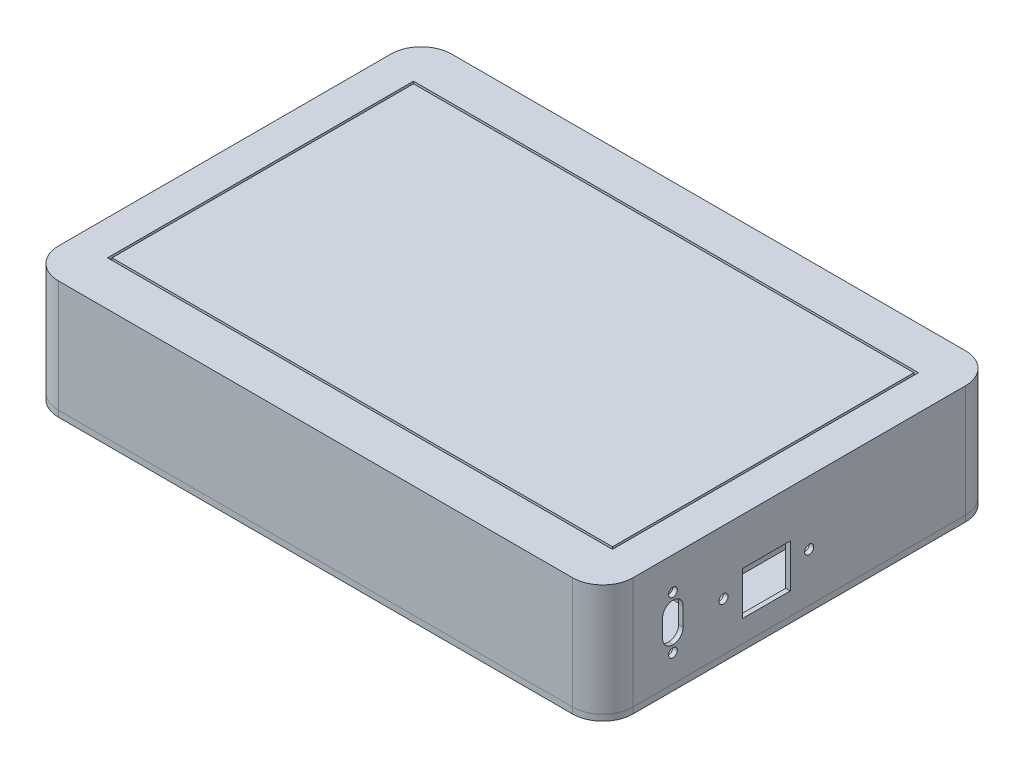
SolidWorks part; units mm, degrees
ref_plane "Front Plane" through (0, 0, 0) normal (0, 0, 1) x (1, 0, 0)
ref_plane "Top Plane" through (0, 0, 0) normal (0, 1, 0) x (1, 0, 0)
ref_plane "Right Plane" through (0, 0, 0) normal (1, 0, 0) x (0, 0, -1)
ref_plane "LCD Plane" through (0, 7.75, 0) normal (0, 1, 0) x (1, 0, 0)
sketch "Sketch1" plane through (0, 0, 0) normal (0, 1, 0) x (1, 0, 0)
  line L0 (-105.3407, -57.4655) -> (-105.3387, -57.4655)
  line L2 (-109.4147, 61.1155) -> (-109.4147, -53.3915)
  line L4 (55.8853, 60.6116) -> (55.8853, -53.3928)
  line L6 (51.7753, -57.4828) -> (51.7953, -57.4828)
  line L7 (-105.3657, 65.1645) -> (-105.3637, 65.1645)
  line L9 (51.7593, 64.7356) -> (51.7613, 64.7356)
  line L10 (-101.2647, -53.3915) -> (-101.2647, -49.5655)
  line L11 (-101.2647, -49.5655) -> (47.6853, -49.5655)
  line L12 (47.6853, -49.5655) -> (47.6853, -53.3928)
  line L13 (-101.3147, 61.1155) -> (-101.3147, 57.2645)
  line L14 (-101.3147, 57.2645) -> (47.6353, 57.2645)
  line L15 (47.6353, 57.2645) -> (47.6353, 60.6116)
  line L17 (-109.4147, 53.9645) -> (55.8853, 53.9645)
  line L18 (-109.4147, 53.9645) -> (-109.4147, -45.6155)
  line L19 (-109.4147, -45.6155) -> (55.8853, -45.6155)
  line L20 (55.8853, 53.9645) -> (55.8853, -45.6155)
  circle A0 centre (-105.2147, -53.7855) radius 1.5
  circle A1 centre (-105.2147, 61.2145) radius 1.5
  circle A2 centre (51.6353, 61.0645) radius 1.5
  circle A3 centre (51.6853, -53.9355) radius 1.5
  arc A4 (-105.3637, 65.1645) -> (-101.3147, 61.1155) centre (-105.3637, 61.1155) cw
  arc A5 (-105.3657, 65.1645) -> (-109.4147, 61.1155) centre (-105.3657, 61.1155) ccw
  arc A6 (51.7613, 64.7356) -> (55.8853, 60.6116) centre (51.7613, 60.6116) cw
  arc A7 (47.6353, 60.6116) -> (51.7593, 64.7356) centre (51.7593, 60.6116) cw
  arc A8 (51.7953, -57.4828) -> (55.8853, -53.3928) centre (51.7953, -53.3928) ccw
  arc A9 (47.6853, -53.3928) -> (51.7753, -57.4828) centre (51.7753, -53.3928) ccw
  arc A10 (-105.3387, -57.4655) -> (-101.2647, -53.3915) centre (-105.3387, -53.3915) ccw
  arc A11 (-109.4147, -53.3915) -> (-105.3407, -57.4655) centre (-105.3407, -53.3915) ccw
  point P24 (0, 0)
  point P25 (0, 0)
  point P26 (0, 0)
  point P27 (0, 0)
  point P28 (0, 0)
  point P29 (0, 0)
  point P30 (0, 0)
  point P33 (-101.3147, 65.1645)
  point P36 (-109.4147, 65.1645)
  point P39 (55.8853, 64.7356)
  point P42 (47.6353, 64.7356)
  point P45 (55.8853, -57.4828)
  point P48 (47.6853, -57.4828)
  point P51 (-101.2647, -57.4655)
  point P54 (-109.4147, -57.4655)
  dimension "D8" = 3
  dimension "D10" = 3
  dimension "D11" = 3
  dimension "D9" = 4.2
  dimension "D12" = 4.25
  dimension "D13" = 3
  dimension "D16" = 115
  dimension "D17" = 3.3
  dimension "D19" = 115
  dimension "D22" = 4.049
  dimension "D23" = 4.124
  dimension "D24" = 4.09
  dimension "D25" = 4.074
  dimension "D1" = 122.63
  dimension "D2" = 8.15
  dimension "D3" = 8.2
  dimension "D4" = 8.1
  dimension "D5" = 7.9
  dimension "D6" = 7.9
  dimension "D7" = 8.25
  dimension "D14" = 4.2
  dimension "D15" = 4.2
  dimension "D18" = 3.95
  dimension "D20" = 7.25
  dimension "D21" = 7.1
extrude "PCB" add sketch "Sketch1" along normal blind 1.75 contours L19 L2 L0 L10 L11 L12 L6 L4 A3 A0 | L2 L19 L4 L17 | L2 L17 L4 L9 L15 L14 L13 L7 A2 A1 region at (-26.7165, 0, 48.3198) region at (-26.7647, 0, -4.1745) region at (-27.0906, 0, -56.3793)
extrude "LCD" add sketch "Sketch1<3>" along normal blind 7.75 contours L19 L20 L17 L18
sketch "Sketch1<3>" plane through (0, 0, 0) normal (0, 1, 0) x (1, 0, 0) same geometry as "Sketch1"
sketch "Sketch2" plane through (0, 0, 0) normal (0, -1, 0) x (1, 0, 0)
  line L0 (-109.4147, -61.1155) -> (-109.4147, 53.3915) construction
  line L1 (-66.7147, 23.0655) -> (15.4353, 23.0655)
  line L2 (-66.7147, 23.0655) -> (-66.7147, -31.0645)
  line L3 (-66.7147, -31.0645) -> (15.4353, -31.0645)
  line L4 (15.4353, 23.0655) -> (15.4353, -31.0645)
  line L5 (-101.3147, -57.2645) -> (47.6353, -57.2645) construction
  line L6 (-101.2647, 49.5655) -> (47.6853, 49.5655) construction
  line L7 (55.8853, -60.6116) -> (55.8853, 53.3928) construction
  dimension "D1" = 42.7
  dimension "D2" = 26.2
  dimension "D3" = 26.5
  dimension "D4" = 40.45
extrude "Pi" add sketch "Sketch2" along normal blind 27 separate body
sketch "Sketch3" plane through (15.4353, 0, 0) normal (1, 0, 0) x (0, 0, -1)
  line L0 (-23.0655, -27) -> (-23.0655, 0) construction
  line L1 (-21.0655, -6.6) -> (28.7145, -6.6)
  line L2 (-21.0655, -6.6) -> (-21.0655, -22)
  line L3 (-21.0655, -22) -> (28.7145, -22)
  line L4 (28.7145, -6.6) -> (28.7145, -22)
  line L5 (31.0645, -27) -> (31.0645, 0) construction
  line L9 (31.0645, 0) -> (-23.0655, 0) construction
  dimension "D1" = 2
  dimension "D2" = 2.35
  dimension "D3" = 6.6
  dimension "D4" = 15.4
extrude "Pi I/O" add sketch "Sketch3" along normal blind 40
sketch "Sketch4" plane through (0, 7.75, 0) normal (0, 1, 0) x (1, 0, 0)
  line L0 (-117.03, -45.2587) -> (-120.1647, -45.2587)
  line L1 (-110.1647, 54.7145) -> (56.6353, 54.7145)
  line L2 (-110.1647, 54.7145) -> (-110.1647, -46.3655)
  line L3 (-110.1647, -46.3655) -> (56.6353, -46.3655)
  line L4 (56.6353, 54.7145) -> (56.6353, -46.3655)
  line L5 (-117.03, -53.2587) -> (-119.4578, -53.2587)
  line L6 (-109.4147, 53.9645) -> (-109.4147, -45.6155) construction
  line L9 (-110.1647, 67.2645) -> (56.6353, 67.2645)
  line L10 (-120.1647, 57.2645) -> (-120.1647, -49.5655)
  line L11 (-110.1647, -59.5655) -> (56.6353, -59.5655)
  line L12 (66.6353, 57.2645) -> (66.6353, -49.5655)
  line L14 (63.5005, -45.2587) -> (66.6353, -45.2587)
  line L15 (-111.6647, 68.7645) -> (58.1353, 68.7645)
  line L16 (-121.6647, 58.7645) -> (-121.6647, -51.0655)
  line L17 (-111.6647, -61.0655) -> (58.1353, -61.0655)
  line L18 (68.1353, 58.7645) -> (68.1353, -51.0655)
  line L21 (63.6353, 61.2645) -> (65.8004, 61.2645)
  line L22 (63.6353, 53.2645) -> (66.6353, 53.2645)
  line L23 (63.5005, -53.2587) -> (65.9283, -53.2587)
  line L26 (-117.1647, 61.2645) -> (-119.3299, 61.2645)
  line L27 (-117.1647, 53.2645) -> (-120.1647, 53.2645)
  line L30 (-109.4147, -45.6155) -> (55.8853, -45.6155) construction
  arc A0 (56.6353, 67.2645) -> (66.6353, 57.2645) centre (56.6353, 57.2645) cw
  arc A1 (58.1353, 68.7645) -> (68.1353, 58.7645) centre (58.1353, 58.7645) cw
  arc A2 (56.6353, -59.5655) -> (66.6353, -49.5655) centre (56.6353, -49.5655) ccw
  arc A3 (58.1353, -61.0655) -> (68.1353, -51.0655) centre (58.1353, -51.0655) ccw
  arc A4 (-120.1647, -49.5655) -> (-110.1647, -59.5655) centre (-110.1647, -49.5655) ccw
  arc A5 (-121.6647, -51.0655) -> (-111.6647, -61.0655) centre (-111.6647, -51.0655) ccw
  arc A6 (-111.6647, 68.7645) -> (-121.6647, 58.7645) centre (-111.6647, 58.7645) ccw
  arc A7 (-110.1647, 67.2645) -> (-120.1647, 57.2645) centre (-110.1647, 57.2645) ccw
  circle A12 centre (63.6353, 57.2645) radius 1.9
  circle A13 centre (-117.1647, 57.2645) radius 1.9
  circle A14 centre (-117.03, -49.2587) radius 1.9
  circle A15 centre (63.5005, -49.2587) radius 1.9
  arc A16 (63.6353, 61.2645) -> (63.6353, 53.2645) centre (63.6353, 57.2645) ccw
  arc A17 (63.5005, -45.2587) -> (63.5005, -53.2587) centre (63.5005, -49.2587) ccw
  arc A19 (-117.1647, 61.2645) -> (-117.1647, 53.2645) centre (-117.1647, 57.2645) cw
  circle A20 centre (-105.2147, 61.2145) radius 4
  circle A21 centre (51.6353, 61.0645) radius 4
  circle A22 centre (-105.2147, -53.7855) radius 4
  circle A23 centre (51.6853, -53.9355) radius 4
  circle A24 centre (-105.2147, 61.2145) radius 1.4
  circle A25 centre (51.6353, 61.0645) radius 1.4
  circle A26 centre (51.6853, -53.9355) radius 1.4
  circle A27 centre (-105.2147, -53.7855) radius 1.4
  arc A28 (-117.03, -45.2587) -> (-117.03, -53.2587) centre (-117.03, -49.2587) cw
  point P7 (0, 0)
  dimension "D13" = 10
  dimension "D14" = 4
  dimension "D15" = 4
  dimension "D16" = 4
  dimension "D17" = 8.9196
  dimension "D20" = 3.8
  dimension "D21" = 3.8
  dimension "D22" = 3.8
  dimension "D23" = 3.8
  dimension "D27" = 4
  dimension "D28" = 8
  dimension "D29" = 2.8
  dimension "D30" = 2.8
  dimension "D31" = 8
  dimension "D32" = 2.8
  dimension "D33" = 8
  dimension "D34" = 8
  dimension "D35" = 2.8
  dimension "D4" = 7.45
  dimension "D6" = 7.45
  dimension "D7" = 7
  dimension "D5" = 10
  dimension "D8" = 10
  dimension "D9" = 1.5
  dimension "D10" = 1.5
  dimension "D11" = 1.5
  dimension "D12" = 1.5
  dimension "D18" = 9.0447
  dimension "D25" = 7.45
  dimension "D26" = 7.45
extrude "Top Face" add sketch "Sketch4" against normal blind 2 separate body contours L2 L3 L4 L1 | L15 A1 L18 A3 L17 A5 L16 A6
extrude "Outer Case" add sketch "Sketch4<17>" against normal blind 37 contours L15 A6 L16 A5 L17 A3 L18 A1 A7 L9 A0 L12 A2 L11 A4 L10 | A19 L26 A7 L10 L27 A13 | L10 A4 A14 | L14 A17 L23 A2 L12 A15 | L21 A16 L22 L12 A0 A12 region at (-113.1372, 7.75, 49.2587) region at (-120.0584, 7.75, -55.2645) region at (64.7144, 7.75, 53.1515) region at (66.3203, 7.75, -59.2859) region at (-26.7647, 7.75, -68.5346)
sketch "Sketch4<17>" plane through (0, 7.75, 0) normal (0, 1, 0) x (1, 0, 0) same geometry as "Sketch4"
extrude "Screen Mounting Holes" add sketch "Sketch4<20>" against normal blind 5.65 contours A22 A27 | A20 A24 | A23 A26 | A21 A25 region at (-109.1016, 7.75, -61.2145) region at (47.7484, 7.75, -61.0645) region at (-109.1016, 7.75, 53.7855) region at (47.7984, 7.75, 53.9355)
sketch "Sketch4<20>" plane through (0, 7.75, 0) normal (0, 1, 0) x (1, 0, 0) same geometry as "Sketch4"
sketch "Sketch6" plane through (0, -29.25, 0) normal (0, -1, 0) x (1, 0, 0)
  line L0 (-121.6647, -58.7645) -> (-121.6647, 51.0655) construction
  line L1 (-111.6647, 61.0655) -> (58.1353, 61.0655)
  line L2 (-121.6647, 51.0655) -> (-121.6647, -58.7645)
  line L3 (-111.6647, -68.7645) -> (58.1353, -68.7645)
  line L4 (68.1353, 51.0655) -> (68.1353, -58.7645)
  line L5 (-111.6647, 61.0655) -> (58.1353, 61.0655) construction
  line L6 (68.1353, -58.7645) -> (68.1353, 51.0655) construction
  line L7 (-111.6647, -68.7645) -> (58.1353, -68.7645) construction
  arc A0 (58.1353, 61.0655) -> (68.1353, 51.0655) centre (58.1353, 51.0655) cw
  arc A1 (58.1353, -68.7645) -> (68.1353, -58.7645) centre (58.1353, -58.7645) ccw
  arc A2 (-121.6647, -58.7645) -> (-111.6647, -68.7645) centre (-111.6647, -58.7645) ccw
  arc A3 (-111.6647, 61.0655) -> (-121.6647, 51.0655) centre (-111.6647, 51.0655) ccw
  circle A4 centre (-117.03, 49.2587) radius 1.9
  circle A5 centre (-117.1647, -57.2645) radius 1.9
  circle A6 centre (63.6353, -57.2645) radius 1.9
  circle A7 centre (63.5005, 49.2587) radius 1.9
  circle A8 centre (-117.03, 49.2587) radius 1.9 construction
  circle A9 centre (-117.1647, -57.2645) radius 1.9 construction
  circle A10 centre (63.6353, -57.2645) radius 1.9 construction
  circle A11 centre (63.5005, 49.2587) radius 1.9 construction
  dimension "D5" = 10
  dimension "D6" = 0
  dimension "D7" = 0
  dimension "D8" = 0
  dimension "D9" = 0
  dimension "D10" = 0
  dimension "D1" = 0
  dimension "D2" = 0
  dimension "D3" = 0
  dimension "D4" = 0
extrude "Rear" add sketch "Sketch6" along normal blind 2 separate body
chamfer "Rear Hole Champfer" distance 2 angle 45 4 edges at (-117.1647, -31.25, -59.1645) (63.6353, -31.25, -59.1645) (63.5005, -31.25, 47.3587) (-117.03, -31.25, 47.3587)
sketch "Sketch7" plane through (0, -31.25, 0) normal (0, -1, 0) x (1, 0, 0)
  line L1 (-121.6647, 51.0655) -> (-121.6647, -58.7645) construction
  line L2 (-111.6647, -68.7645) -> (58.1353, -68.7645) construction
  text T0 "<b>While our photos may get lost, </b>\r\n<b>our memories will last forever</b>\r\n\r\n<b>With Love, </b>\r\n<b>Soren</b>\r\n<b>Christmas 2022</b>\r\n" font "Tw Cen MT" height 5
  point P5 (-107.6647, -28.7645)
  point P7 (-104.6439, -33.2658)
  dimension "D1" = 14
  dimension "D2" = 57
extrude "Text" cut sketch "Sketch7" against normal blind 0.5
sketch "Sketch9" plane through (66.6353, 0, 0) normal (-1, 0, 0) x (0, 0, 1)
  line L0 (-53.2645, -29.25) -> (45.2587, -29.25) construction
  line L1 (33.8419, 0.95) -> (41.9419, 0.95)
  line L2 (33.8419, 0.95) -> (33.8419, -24.25)
  line L3 (33.8419, -24.25) -> (41.9419, -24.25)
  line L4 (41.9419, 0.95) -> (41.9419, -24.25)
  line L6 (33.8419, -5.3) -> (41.9419, -5.3)
  line L7 (33.8419, -5.3) -> (33.8419, -18)
  line L8 (33.8419, -18) -> (41.9419, -18)
  line L9 (41.9419, -5.3) -> (41.9419, -18)
  line L10 (37.8419, -5.3) -> (37.9419, -5.3)
  line L11 (34.4919, -8.65) -> (34.4919, -14.65)
  line L12 (37.8419, -18) -> (37.9419, -18)
  line L13 (41.2919, -8.65) -> (41.2919, -14.65)
  line L14 (-11.3149, -2.25) -> (25.3851, -2.25)
  line L15 (-11.3149, -2.25) -> (-11.3149, -24.25)
  line L16 (-11.3149, -24.25) -> (25.3851, -24.25)
  line L17 (25.3851, -2.25) -> (25.3851, -24.25)
  line L18 (-0.8649, -7.7) -> (14.9351, -7.7)
  line L19 (-0.8649, -7.7) -> (-0.8649, -22)
  line L20 (-0.8649, -22) -> (14.9351, -22)
  line L21 (14.9351, -7.7) -> (14.9351, -22)
  circle A0 centre (37.87, -3) radius 1.45
  circle A1 centre (37.8919, -20.3) radius 1.45
  circle A2 centre (-7.1149, -13.25) radius 1.5
  circle A3 centre (21.1851, -13.25) radius 1.5
  arc A4 (37.9419, -18) -> (41.2919, -14.65) centre (37.9419, -14.65) ccw
  arc A5 (34.4919, -14.65) -> (37.8419, -18) centre (37.8419, -14.65) ccw
  arc A6 (37.9419, -5.3) -> (41.2919, -8.65) centre (37.9419, -8.65) cw
  arc A7 (37.8419, -5.3) -> (34.4919, -8.65) centre (37.8419, -8.65) ccw
  point P26 (0, 0)
  point P33 (41.2919, -18)
  point P40 (34.4919, -5.3)
  dimension "D6" = 4.05
  dimension "D15" = 3
  dimension "D16" = 3
  dimension "D25" = 3.35
  dimension "D1" = 25.2
  dimension "D2" = 5
  dimension "D3" = 8.1
  dimension "D4" = 6.25
  dimension "D5" = 6.25
  dimension "D7" = 4.028
  dimension "D8" = 3.95
  dimension "D9" = 3.95
  dimension "D10" = 0.65
  dimension "D11" = 0.65
  dimension "D12" = 36.7
  dimension "D13" = 22
  dimension "D14" = 5
  dimension "D17" = 4.2
  dimension "D18" = 4.2
  dimension "D19" = 11
  dimension "D20" = 11
  dimension "D21" = 10.45
  dimension "D22" = 10.45
  dimension "D23" = 5.45
  dimension "D24" = 2.25
extrude "Cut-Extrude2" cut sketch "Sketch9" against normal through all contours A2 | L21 L18 L19 L20 | A3 | A0 | L13 L6 L11 L8 | A1 region at (66.6353, -11.65, 37.8919) region at (66.6353, -14.85, 7.0351) region at (66.6353, -3, 37.87) region at (66.6353, -20.3, 37.8919) region at (66.6353, -13.25, -7.1149) region at (66.6353, -13.25, 21.1851)
